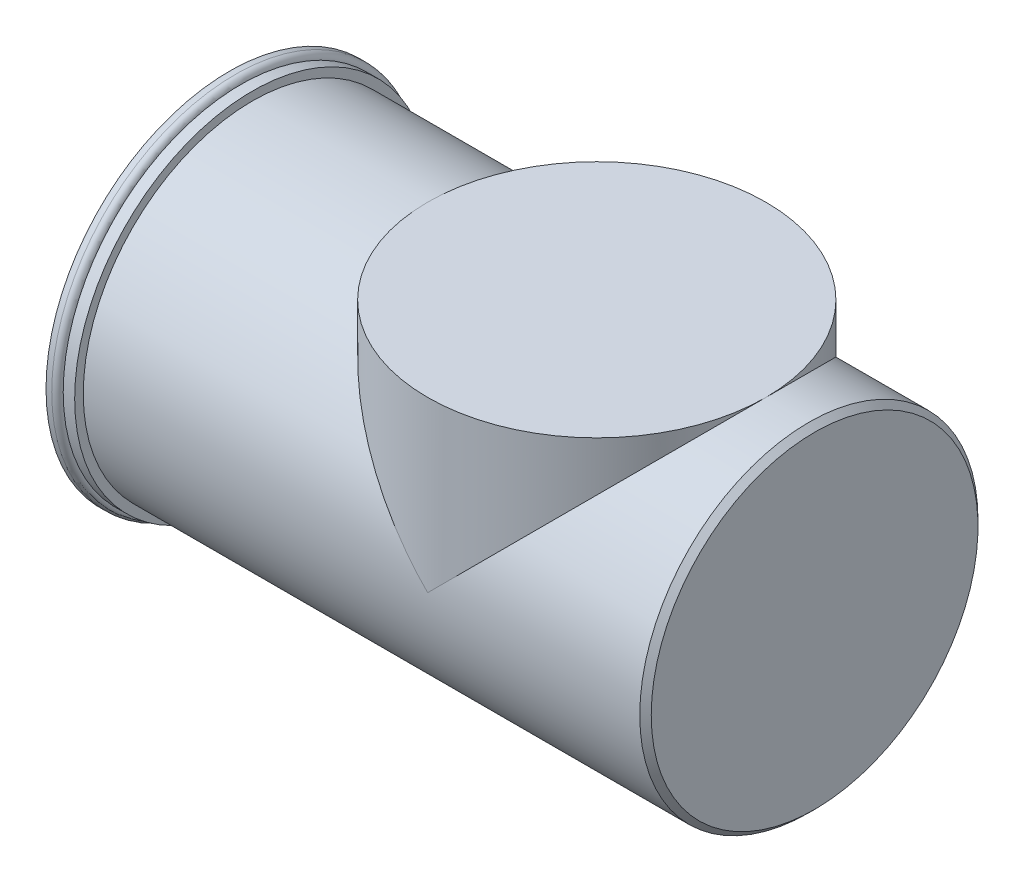
SolidWorks part; units mm, degrees
ref_plane "Alzado" through (0, 0, 0) normal (0, 0, 1) x (1, 0, 0)
ref_plane "Planta" through (0, 0, 0) normal (0, 1, 0) x (1, 0, 0)
ref_plane "Vista lateral" through (0, 0, 0) normal (1, 0, 0) x (0, 0, -1)
sketch "Croquis3" plane through (0, 0, 0) normal (1, 0, 0) x (0, 0, -1)
  circle A0 centre (0, 0) radius 74.93
  dimension "D1" = 149.86
extrude "Saliente-Extruir3" add sketch "Croquis3" along normal blind 96.52 and the other way blind 152.59
ref_plane "Plano1" through (0, 74.93, 0) normal (0, 1, 0) x (1, 0, 0)
sketch "Croquis4" plane through (0, 74.93, 0) normal (0, 1, 0) x (1, 0, 0)
  circle A0 centre (0, 0) radius 74.93
extrude "Saliente-Extruir4" add sketch "Croquis4" against normal up to surface (74.93 mm away) up to face at (-152.59, 0, -74.93)
sketch "Croquis5" plane through (-152.59, 0, 0) normal (-1, 0, 0) x (0, 0, 1)
  circle A0 centre (0, 0) radius 78.74
  dimension "D1" = 157.48
extrude "Saliente-Extruir5" add sketch "Croquis5" along normal blind 5.08
sketch "Croquis6" plane through (-157.67, 0, 0) normal (-1, 0, 0) x (0, 0, 1)
  circle A0 centre (0, 0) radius 81.28
  dimension "D1" = 162.56
extrude "Saliente-Extruir6" add sketch "Croquis6" along normal blind 5.08
fillet "Redondeo1" radius 2.54 1 edges at (-157.67, 0, 81.28)
chamfer "Chaflán1" distance 2.54 angle 45 1 edges at (96.52, 0, -74.93)
ref_axis "Link1-line1" through (-152.59, 0, 0) along (1, 0, 0)
ref_axis "Link1-line2" through (0, 0, 0) along (0, 1, 0)
ref_point "Link1-point1"
